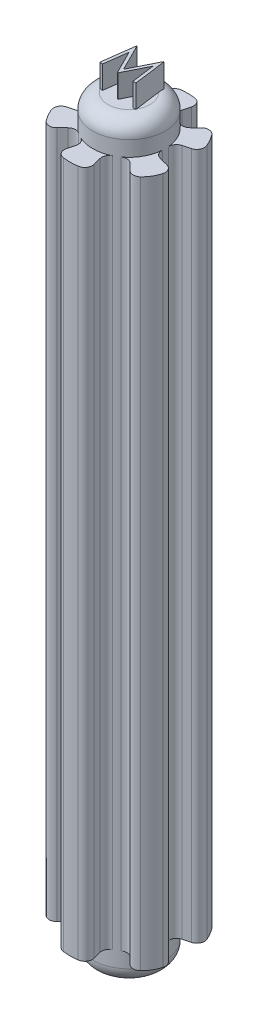
SolidWorks part; units mm, degrees
ref_plane "Front Plane" through (0, 0, 0) normal (0, 0, 1) x (1, 0, 0)
ref_plane "Top Plane" through (0, 0, 0) normal (0, 1, 0) x (1, 0, 0)
ref_plane "Right Plane" through (0, 0, 0) normal (1, 0, 0) x (0, 0, -1)
sketch "Sketch2" plane through (0, 0, 0) normal (0, 1, 0) x (1, 0, 0)
  line L0 (0, 0) -> (0.0739, 0)
  line L2 (2.3008, -0.5891) -> (3.7752, -0.9786)
  line L3 (0.0739, 0) -> (0.1042, -0.0303)
  line L4 (0, 0) -> (0.0858, -0.0446)
  line L5 (1.6802, 1.6786) -> (2.7413, 2.7388)
  line L6 (-1.6794, 1.6794) -> (-2.74, 2.74)
  line L8 (0.6147, 2.2941) -> (1.0029, 3.743)
  line L9 (-0.6147, 2.2941) -> (-1.0029, 3.743)
  line L10 (2.2941, 0.6147) -> (3.743, 1.0029)
  line L11 (0, 0) -> (0.1042, -0.0303)
  line L12 (-2.2941, 0.6147) -> (-3.743, 1.0029)
  line L13 (0.0739, 0) -> (0.0858, -0.0446)
  line L14 (-0.6147, -2.2941) -> (-1.0029, -3.743)
  line L15 (-2.2941, -0.6147) -> (-3.743, -1.0029)
  line L16 (-1.6794, -1.6794) -> (-2.74, -2.74)
  line L17 (0.6814, -2.2752) -> (1.0684, -3.7248)
  line L18 (1.7145, -1.6435) -> (2.7672, -2.6981)
  arc A0 (-2.2941, 0.6147) -> (-2.2941, -0.6147) centre (0, 0) ccw
  arc A1 (-2.74, 2.74) -> (-3.743, 1.0029) centre (0, 0) ccw
  arc A2 (1.0029, 3.743) -> (-1.0029, 3.743) centre (0, 0) ccw
  arc A3 (3.743, 1.0029) -> (2.7413, 2.7388) centre (0, 0) ccw
  arc A5 (-1.0029, -3.743) -> (1.0684, -3.7248) centre (0, 0) ccw
  arc A6 (-3.743, -1.0029) -> (-2.74, -2.74) centre (0, 0) ccw
  arc A7 (-2.74, 2.74) -> (-3.743, 1.0029) centre (0, 0) ccw
  arc A8 (1.0029, 3.743) -> (-1.0029, 3.743) centre (0, 0) ccw
  arc A9 (3.743, 1.0029) -> (2.7413, 2.7388) centre (0, 0) ccw
  arc A10 (-3.743, -1.0029) -> (-2.74, -2.74) centre (0, 0) ccw
  arc A11 (-1.0029, -3.743) -> (1.0684, -3.7248) centre (0, 0) ccw
  arc A12 (2.7672, -2.6981) -> (3.7752, -0.9786) centre (1.7753, -0.9614) ccw
  arc A13 (-0.6147, 2.2941) -> (-1.6794, 1.6794) centre (0, 0) ccw
  arc A14 (1.6802, 1.6786) -> (0.6147, 2.2941) centre (0, 0) ccw
  arc A15 (2.3008, -0.5891) -> (2.2941, 0.6147) centre (0, 0) ccw
  arc A16 (0.6814, -2.2752) -> (1.7145, -1.6435) centre (0, 0) ccw
  arc A17 (-1.6794, -1.6794) -> (-0.6147, -2.2941) centre (0, 0) ccw
  dimension "D1" = 3.875
  dimension "D2" = 2.375
extrude "Boss-Extrude1" add sketch "Sketch2" along normal blind 45 contours L16 A17 L14 A5 L17 A16 L18 A12 L2 A15 L10 A3 L5 A14 L8 A2 L9 A13 L6 A1 L12 A0 L15 A6 L11 L13 L4 L0 L3 region at (0.0225, 0, 0.0171)
sketch "Sketch4" plane through (0, 45, 0) normal (0, 1, 0) x (1, 0, 0)
  circle A0 centre (0, 0) radius 2.375
  dimension "D1" = 4.75
extrude "Boss-Extrude3" add sketch "Sketch4" along normal blind 2
fillet "Fillet1" radius 0.5 24 edges at (-2.74, 22.5, -2.74) (-1.6794, 22.5, -1.6794) (-0.6147, 22.5, -2.2941) (-1.0029, 22.5, -3.743) (1.0029, 22.5, -3.743) (0.6147, 22.5, -2.2941) (1.6802, 22.5, -1.6786) (2.7413, 22.5, -2.7388) (3.743, 22.5, -1.0029) (2.2941, 22.5, -0.6147) (2.3008, 22.5, 0.5891) (3.7752, 22.5, 0.9786) (2.7672, 22.5, 2.6981) (1.7145, 22.5, 1.6435) (0.6814, 22.5, 2.2752) (-1.6794, 22.5, 1.6794) (-2.2941, 22.5, 0.6147) (-2.2941, 22.5, -0.6147) (-0.6147, 22.5, 2.2941) (-3.743, 22.5, -1.0029) (-3.743, 22.5, 1.0029) (-2.74, 22.5, 2.74) (-1.0029, 22.5, 3.743) (1.0684, 22.5, 3.7248)
sketch "Sketch5" plane through (0, 47, 0) normal (0, 1, 0) x (1, 0, 0)
  text T0 "M" font "Century Gothic" height in points 8
extrude "Boss-Extrude4" add sketch "Sketch5" along normal blind 1.5
sketch "Sketch6" plane through (0, 0, 0) normal (0, -1, 0) x (1, 0, 0)
  circle A0 centre (0, 0) radius 2.375
  dimension "D1" = 4.75
extrude "Boss-Extrude5" add sketch "Sketch6" along normal blind 2
fillet "Fillet2" radius 1 2 edges at (0, 47, 2.375) (0, -2, -2.375)
